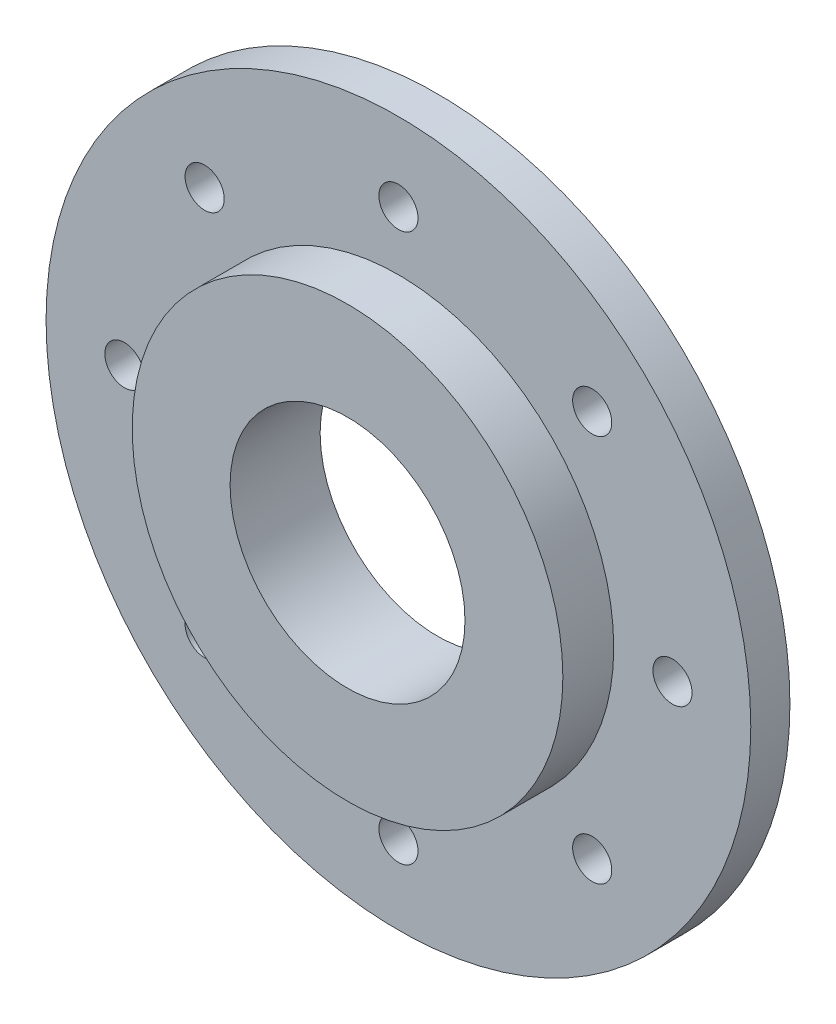
SolidWorks part; units mm, degrees
ref_plane "Front Plane" through (0, 0, 0) normal (0, 0, 1) x (1, 0, 0)
ref_plane "Top Plane" through (0, 0, 0) normal (0, 1, 0) x (1, 0, 0)
ref_plane "Right Plane" through (0, 0, 0) normal (1, 0, 0) x (0, 0, -1)
sketch "Sketch1" plane through (0, 0, 0) normal (0, 0, 1) x (1, 0, 0)
  circle A0 centre (0, 0) radius 17.4625
  dimension "D1" = 34.925
extrude "Boss-Extrude1" add sketch "Sketch1" along normal blind 4.1275
sketch "Sketch2" plane through (0, 0, 0) normal (0, 0, -1) x (-1, 0, 0)
  circle A0 centre (0, 0) radius 28.575
  dimension "D1" = 57.15
extrude "Boss-Extrude2" add sketch "Sketch2" along normal blind 3.175
hole_wizard "1/8 (0.125) Diameter Hole1" positions "Sketch3" profile "Sketch4" hole size "1/8" standard "ANSI Inch" end condition through all
sketch "Sketch3" plane through (0, 0, -3.175) normal (0, 0, -1) x (-1, 0, 0)
  point P0 (0, 22.225)
  dimension "D1" = 22.225
sketch "Sketch4" plane through (0, 22.225, -3.175) normal (1, 0, 0) x (0, 1, 0)
  line L0 (0, 0) -> (0, 7.3025)
  line L1 (0, 7.3025) -> (1.5875, 7.3025)
  line L2 (1.5875, 7.3025) -> (1.5875, 0)
  line L5 (1.5875, 0) -> (0, 0)
  line L11 (0, -6.35) -> (0, 107.95) construction
  dimension "Thru Hole Dia." = 3.175
  dimension "Thru Hole Depth" = 7.3025
pattern_circular "CirPattern1" count 8 over 360 about axis through (0, 0, -3.175) along (0, 0, -1) of "1/8 (0.125) Diameter Hole1"
sketch "Sketch5" plane through (0, 0, -3.175) normal (0, 0, -1) x (-1, 0, 0)
  circle A0 centre (0, 0) radius 9.525
  dimension "D1" = 19.05
extrude "Cut-Extrude1" cut sketch "Sketch5" against normal up to next
